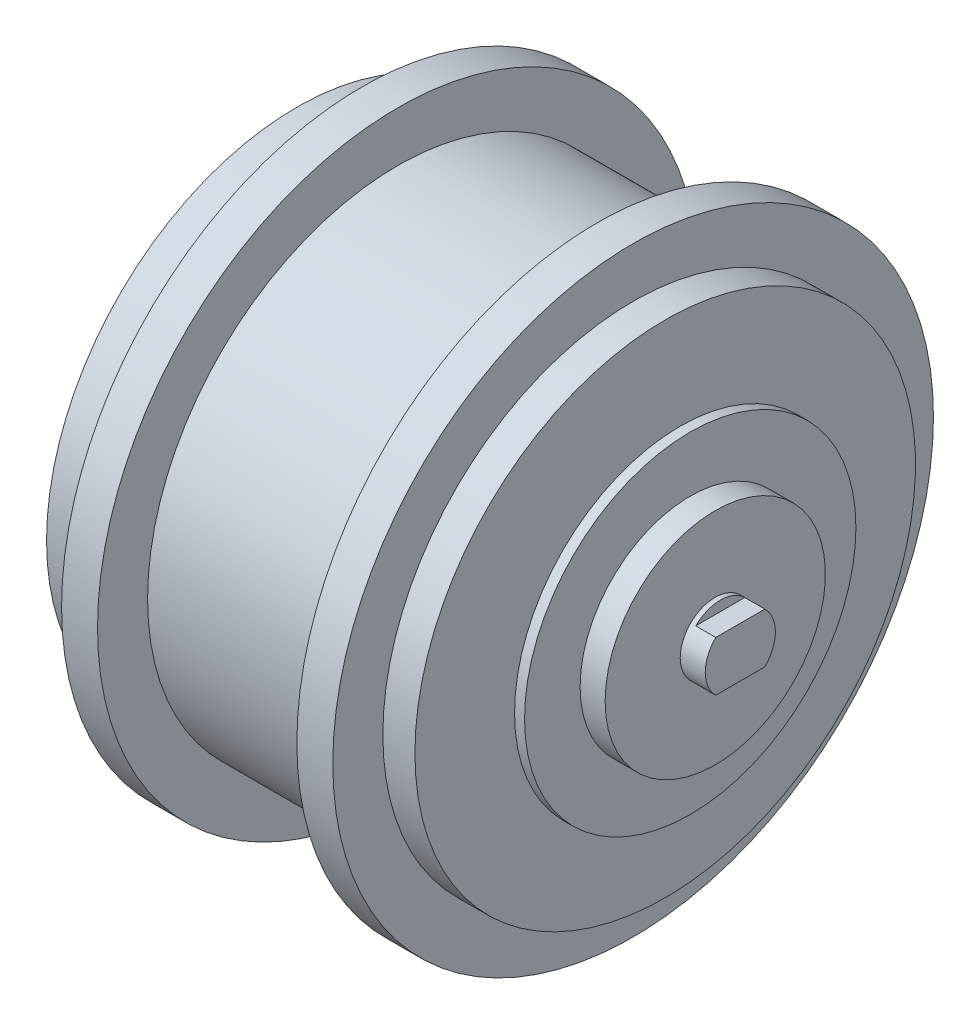
SolidWorks part; units mm, degrees
ref_plane "Front Plane" through (0, 0, 0) normal (0, 0, 1) x (1, 0, 0)
ref_plane "Top Plane" through (0, 0, 0) normal (0, 1, 0) x (1, 0, 0)
ref_plane "Right Plane" through (0, 0, 0) normal (1, 0, 0) x (0, 0, -1)
sketch "Sketch1" plane through (0, 0, 0) normal (0, 0, 1) x (1, 0, 0)
  line L0 (0, 0) -> (219.0485, 0) construction
  line L1 (0, 0) -> (0, 6)
  line L2 (0, 6) -> (33, 6)
  line L3 (33, 6) -> (33, 8.5)
  line L4 (33, 8.5) -> (43.5, 8.5)
  line L5 (66.569, 50) -> (66.569, 60)
  line L6 (73.751, 60) -> (66.569, 60)
  line L7 (73.751, 60) -> (73.751, 50)
  line L8 (66.569, 50) -> (53.569, 50)
  line L9 (53.569, 50) -> (46.5, 36.3186)
  line L10 (43.5, 8.5) -> (43.5, 17)
  line L11 (43.5, 17) -> (46.5, 17)
  line L12 (46.5, 17) -> (46.5, 36.3186)
  line L13 (73.751, 50) -> (113.569, 50)
  line L14 (113.569, 50) -> (113.569, 60)
  line L15 (113.569, 60) -> (120.751, 60)
  line L16 (120.751, 60) -> (120.751, 50)
  line L17 (120.751, 50) -> (127.16, 50)
  line L18 (127.16, 50) -> (127.16, 22)
  line L19 (127.16, 22) -> (130.16, 22)
  line L20 (137.16, 22) -> (137.16, 7)
  line L21 (137.16, 7) -> (142.16, 7)
  line L22 (142.16, 7) -> (142.16, 0)
  line L23 (130.16, 22) -> (130.16, 33.1)
  line L24 (130.16, 33.1) -> (132.16, 33.1)
  line L25 (142.16, 0) -> (0, 0)
  line L26 (132.16, 33.1) -> (132.16, 22)
  line L27 (132.16, 22) -> (137.16, 22)
  point P13 (70.16, 60)
  point P23 (117.16, 60)
  dimension "D1" = 33
  dimension "D2" = 8.5
  dimension "D3" = 10.5
  dimension "D4" = 26.66
  dimension "D5" = 60
  dimension "D6" = 60
  dimension "D7" = 13
  dimension "D8" = 33.1
  dimension "D9" = 47
  dimension "D10" = 10
  dimension "D11" = 22
  dimension "D12" = 10
  dimension "D13" = 6
  dimension "D14" = 5
  dimension "D15" = 2
  dimension "D16" = 7
  dimension "D17" = 5
  dimension "D18" = 50
  dimension "D19" = 17
revolve "Revolve1" add sketch "Sketch1" angle 360 about L0
sketch "Sketch2" plane through (142.16, 0, 0) normal (1, 0, 0) x (0, 0, -1)
  line L0 (-4.899, 5) -> (4.899, 5)
  line L1 (-4.899, -5) -> (4.899, -5)
  circle A0 centre (0, 0) radius 7 construction
  circle A1 centre (0, 0) radius 7 construction
  arc A2 (-4.899, -5) -> (4.899, -5) centre (0, 0) ccw
  arc A3 (4.899, 5) -> (-4.899, 5) centre (0, 0) ccw
  dimension "D1" = 10
extrude "Cut-Extrude1" cut sketch "Sketch2" against normal blind 4
sketch "Sketch3" plane through (33, 0, 0) normal (-1, 0, 0) x (0, 0, 1)
  circle A0 centre (0, 0) radius 8.5 construction
  circle A1 centre (0, 0) radius 8.5
extrude "Cut-Extrude2" cut sketch "Sketch3" against normal blind 3 and the other way through all
